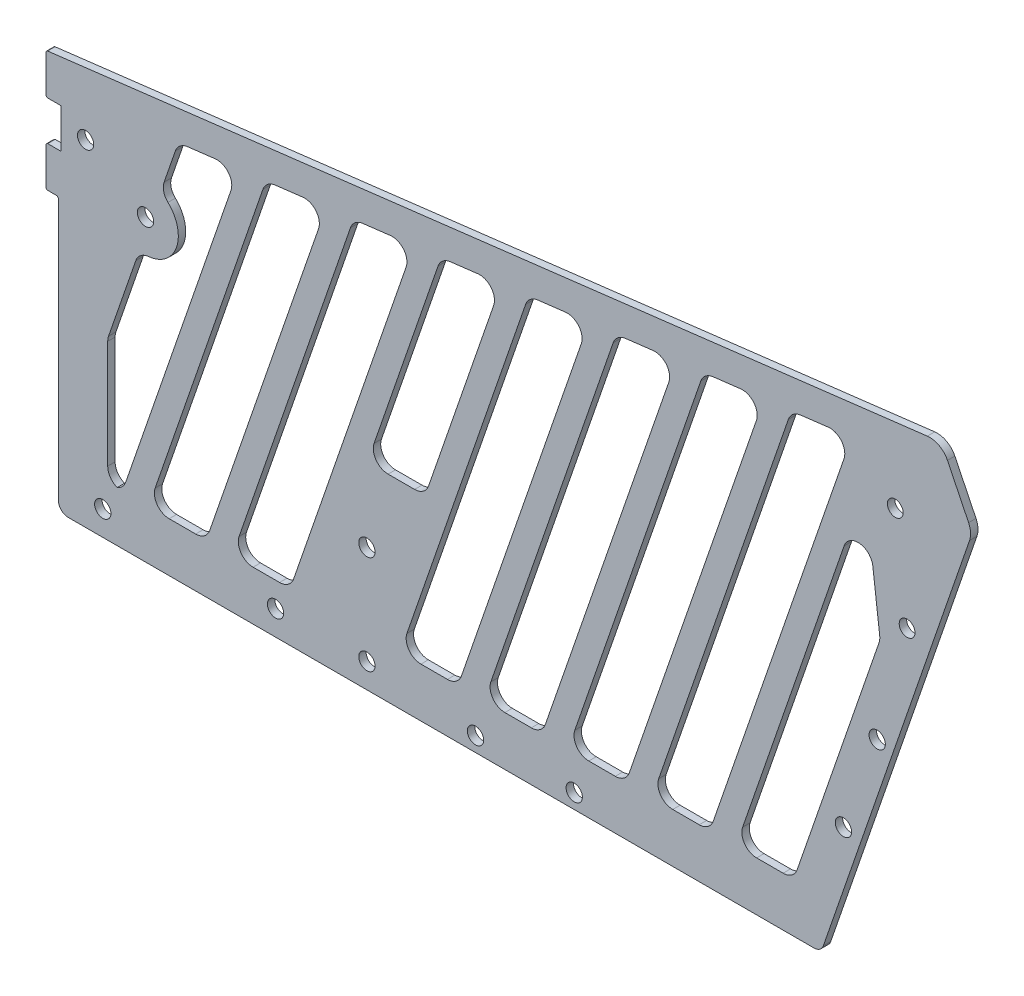
SolidWorks part; units mm, degrees
other "标注1"
sketch "草图8" plane through (190, 0, 1.5) normal (0.4662, -0.1687, 0.8685) x (0.883, 0.0286, -0.4684)
material "自定义塑料"
ref_plane "前视基准面" through (0, 0, 0) normal (0, 0, 1) x (1, 0, 0)
ref_plane "上视基准面" through (0, 0, 0) normal (0, 1, 0) x (1, 0, 0)
ref_plane "右视基准面" through (0, 0, 0) normal (1, 0, 0) x (0, 0, -1)
sketch "草图1" plane through (0, 0, 0) normal (0, 0, 1) x (1, 0, 0)
  line L0 (44, 5) -> (9, 5) construction
  line L1 (0, 0) -> (49, 0)
  line L2 (0, 0) -> (0, 80)
  line L5 (49, 0) -> (154.5, 0)
  line L6 (154.5, 0) -> (190, 102.9694)
  line L7 (0, 80) -> (190, 102.9694)
  circle A0 centre (44, 5) radius 1.65
  circle A1 centre (9, 5) radius 1.65
  circle A2 centre (62.5, 5) radius 1.65
  circle A3 centre (62.5, 25) radius 1.65
  circle A4 centre (84.5, 3) radius 1.65
  circle A5 centre (104.5, 3) radius 1.65
  circle A6 centre (159.0292, 24.1724) radius 1.65
  circle A7 centre (165.8696, 42.9663) radius 1.65
  circle A8 centre (5.5167, 68) radius 1.65
  point P9 (173.819, 56.0356)
  dimension "D3" = 3.3
  dimension "D4" = 190
  dimension "D1" = 49
  dimension "D2" = 80
  dimension "D5" = 5
  dimension "D6" = 35
  dimension "D7" = 105.5
extrude "凸台-拉伸1" add sketch "草图1" along normal blind 1.5
sketch "草图2" plane through (0, 0, 0) normal (0, 0, -1) x (-1, 0, 0)
  circle A0 centre (-17.6548, 60.5226) radius 1.65
  dimension "D1" = 3.3
  dimension "D2" = 60.5226
  dimension "D3" = 17.6548
extrude "切除-拉伸1" cut sketch "草图2" against normal through all
sketch "草图5" plane through (0, 0, 1.5) normal (0, 0, 1) x (1, 0, 0)
  line L0 (0, 80) -> (0, 0) construction
  line L1 (0, 0) -> (154.5, 0) construction
  circle A0 centre (169.5262, 85.385) radius 1.6
  circle A1 centre (171.9266, 65.5296) radius 1.6
  dimension "D1" = 3.2
  dimension "D2" = 169.5262
  dimension "D3" = 171.9266
  dimension "D4" = 65.5296
  dimension "D5" = 85.385
extrude "切除-拉伸3" cut sketch "草图5" against normal through all
sketch "草图6" plane through (0, 0, 0) normal (0, 0, -1) x (-1, 0, 0)
  line L0 (-154.5, 10) -> (0, 10)
  line L1 (-10, 0) -> (-10, 80)
  line L2 (-0.7201, 74.0434) -> (-181.2031, 95.8622)
  line L3 (-181.2031, 95.8622) -> (-148.8277, 1.9556)
  line L4 (0, 0) -> (0, 80)
  line L5 (-154.5, 0) -> (0, 0)
  line L6 (-190, 102.9694) -> (-154.5, 0)
  line L7 (0, 80) -> (-190, 102.9694)
  line L8 (0, 0) -> (0, 80)
  line L9 (-154.5, 0) -> (0, 0)
  line L10 (-190, 102.9694) -> (-154.5, 0)
  line L11 (0, 80) -> (-190, 102.9694)
  line L12 (-162.4894, 93.5999) -> (-167.1453, 55.0868)
  line L13 (-164.2031, 95.8622) -> (-131.8277, 1.9556)
  line L14 (-147.2031, 95.8622) -> (-114.8277, 1.9556)
  line L15 (-130.2031, 95.8622) -> (-97.8277, 1.9556)
  line L16 (-113.2031, 95.8622) -> (-80.8277, 1.9556)
  line L17 (-96.2031, 95.8622) -> (-63.8277, 1.9556)
  line L18 (-79.2031, 95.8622) -> (-46.8277, 1.9556)
  line L19 (-62.2031, 95.8622) -> (-29.8277, 1.9556)
  line L20 (-45.2031, 95.8622) -> (-12.8277, 1.9556)
  line L21 (-28.2031, 95.8622) -> (4.1723, 1.9556)
  line L22 (-166.5666, 95.0474) -> (-134.1912, 1.1408)
  line L23 (-149.5666, 95.0474) -> (-117.1912, 1.1408)
  line L24 (-132.5666, 95.0474) -> (-100.1912, 1.1408)
  line L25 (-115.5666, 95.0474) -> (-83.1912, 1.1408)
  line L26 (-98.5666, 95.0474) -> (-66.1912, 1.1408)
  line L27 (-81.5666, 95.0474) -> (-49.1912, 1.1408)
  line L28 (-64.5666, 95.0474) -> (-32.1912, 1.1408)
  line L29 (-47.5666, 95.0474) -> (-15.1912, 1.1408)
  line L30 (-30.5666, 95.0474) -> (1.8088, 1.1408)
  line L31 (-161.8397, 96.6771) -> (-129.4642, 2.7705)
  line L32 (-144.8397, 96.6771) -> (-112.4642, 2.7705)
  line L33 (-127.8397, 96.6771) -> (-95.4642, 2.7705)
  line L34 (-110.8397, 96.6771) -> (-78.4642, 2.7705)
  line L35 (-93.8397, 96.6771) -> (-61.4642, 2.7705)
  line L36 (-76.8397, 96.6771) -> (-44.4642, 2.7705)
  line L37 (-59.8397, 96.6771) -> (-27.4642, 2.7705)
  line L38 (-42.8397, 96.6771) -> (-10.4642, 2.7705)
  line L39 (-25.8397, 96.6771) -> (6.5358, 2.7705)
  line L40 (-178.8397, 96.6771) -> (-146.4642, 2.7705)
  circle A0 centre (-169.5262, 85.385) radius 1.6 construction
  circle A1 centre (-171.9266, 65.5296) radius 1.6 construction
  circle A2 centre (-165.8696, 42.9663) radius 1.5 construction
  circle A3 centre (-159.0292, 24.1724) radius 1.5 construction
  circle A4 centre (-104.5, 3) radius 1.65 construction
  circle A5 centre (-84.5, 3) radius 1.65 construction
  circle A6 centre (-62.5, 5) radius 1.65 construction
  circle A7 centre (-44, 5) radius 1.65 construction
  circle A8 centre (-62.5, 25) radius 1.65 construction
  circle A9 centre (-9, 5) radius 1.65 construction
  circle A10 centre (-17.6548, 60.5226) radius 1.65 construction
  circle A11 centre (-5.5167, 68) radius 1.65 construction
  circle A12 centre (-169.5262, 85.385) radius 1.6
  circle A13 centre (-171.9266, 65.5296) radius 1.6
  circle A14 centre (-165.8696, 42.9663) radius 1.5
  circle A15 centre (-159.0292, 24.1724) radius 1.5
  circle A16 centre (-104.5, 3) radius 1.65
  circle A17 centre (-84.5, 3) radius 1.65
  circle A18 centre (-62.5, 5) radius 1.65
  circle A19 centre (-44, 5) radius 1.65
  circle A20 centre (-62.5, 25) radius 1.65
  circle A21 centre (-9, 5) radius 1.65
  circle A22 centre (-17.6548, 60.5226) radius 1.65
  circle A23 centre (-5.5167, 68) radius 1.65
  circle A24 centre (-17.6548, 60.5226) radius 6.65
  circle A25 centre (-62.5, 25) radius 6.65
  dimension "D5" = 6
  dimension "D11" = 13.5717
  dimension "D1" = 0
  dimension "D2" = 10
  dimension "D3" = 10
  dimension "D4" = 6
  dimension "D7" = 2.5
  dimension "D8" = 2.5
  dimension "D9" = 5
  dimension "D10" = 2.5
  dimension "D6" = 10
extrude "切除-拉伸4" cut sketch "草图6" against normal blind 10 contours A24 L30 L2 L38 L0 L1 | L2 L37 L0 L29 | L2 L36 L0 L28 | A25 L27 L2 L35 | L2 L34 L0 L26 | L2 L33 L0 L25 | L2 L32 L0 L24 | L2 L31 L0 L23 | L22 L12 L3 L0 region at (153.7758, 42.0864, 0) region at (140.3654, 51.3238, 0) region at (122.9962, 50.2516, 0) region at (105.627, 49.1793, 0) region at (88.2579, 48.1071, 0) region at (74.454, 57.0811, 0) region at (20.6801, 46.912, 0) region at (53.5197, 45.9626, 0) region at (36.1506, 44.8904, 0)
fillet "圆角3" radius 3 37 edges at (89.747, 84.806, 0.75) (77.5264, 83.3286, 0.75) (69.2455, 10, 0.75) (80.9567, 10, 0.75) (107.4863, 86.9505, 0.75) (95.2658, 85.4731, 0.75) (18.2455, 10, 0.75) (29.9567, 10, 0.75) (54.2682, 80.5169, 0.75) (42.0477, 79.0395, 0.75) (35.2455, 10, 0.75) (46.9567, 10, 0.75) (72.0076, 82.6614, 0.75) (59.7871, 81.1841, 0.75) (120.2455, 10, 0.75) (131.9567, 10, 0.75) (160.7044, 93.3841, 0.75) (148.4839, 91.9067, 0.75) (16.4115, 53.9898, 0.75) (10, 35.3929, 0.75) (10, 10, 0.75) (12.9567, 10, 0.75) (36.5289, 78.3723, 0.75) (24.3084, 76.895, 0.75) (20.7016, 66.4335, 0.75) (103.2455, 10, 0.75) (114.9567, 10, 0.75) (142.965, 91.2396, 0.75) (130.7445, 89.7622, 0.75) (86.2455, 10, 0.75) (97.9567, 10, 0.75) (125.2257, 89.095, 0.75) (113.0051, 87.6177, 0.75) (163.4184, 85.9157, 0.75) (137.2455, 10, 0.75) (166.4588, 60.7657, 0.75) (148.9567, 10, 0.75)
fillet "圆角4" radius 5 1 edges at (69.1497, 25.0627, 0.75)
sketch "草图7" plane through (0, 0, 1.5) normal (0, 0, 1) x (1, 0, 0)
  line L1 (76.1407, 40) -> (59.1407, 40)
  line L2 (76.1407, 40) -> (76.1407, 30)
  line L3 (76.1407, 30) -> (59.1407, 30)
  line L4 (59.1407, 40) -> (59.1407, 30)
  line L6 (0, 0) -> (154.5, 0) construction
  line L7 (94.6538, 83.698) -> (70.6169, 13.9778) construction
  dimension "D1" = 40
  dimension "D2" = 17
  dimension "D3" = 10
extrude "凸台-拉伸2" add sketch "草图7" against normal up to surface (1.5 mm away) up to face at (88.1355, 48.0309, 0)
fillet "圆角5" radius 3 2 edges at (74.2996, 40, 0.75) (62.5884, 40, 0.75)
fillet "圆角7" radius 2 3 edges at (154.5, 0, 0.75) (0, 0, 0.75) (0, 80, 0.75)
chamfer "倒角1" distance 15 angle 45 1 edges at (190, 102.9694, 0.75) first distance on face at (172.4824, 52.1587, 0.75)
fillet "圆角8" radius 4 2 edges at (178.8576, 101.6224, 0.75) (185.111, 88.7885, 0.75)
sketch "草图9" plane through (0, 0, 1.5) normal (0, 0, 1) x (1, 0, 0)
  line L0 (0, 78.2272) -> (0, 2) construction
  line L1 (-0.5, 63.5) -> (0.5, 63.5)
  line L2 (-0.5, 63.5) -> (-0.5, 71.5)
  line L3 (-0.5, 71.5) -> (0.5, 71.5)
  line L4 (0.5, 63.5) -> (0.5, 71.5)
  line L5 (-0.5, 63.5) -> (0.5, 71.5) construction
  line L6 (-0.5, 71.5) -> (0.5, 63.5) construction
  circle A0 centre (5.5167, 68) radius 1.65 construction
  point P0 (0, 67.5)
  dimension "D2" = 4.5
  dimension "D1" = 3.5
  dimension "D3" = 0.5
extrude "切除-拉伸5" cut sketch "草图9" against normal blind 10
sketch "草图10" plane through (0, 0, 1.5) normal (0, 0, 1) x (1, 0, 0)
  line L0 (1.76, 80.2128) -> (-2.5, 79.6978)
  line L1 (-2.5, 79.6978) -> (-2.5, 71.5)
  line L2 (-2.5, 71.5) -> (0, 71.5)
  line L3 (0, 63.5) -> (-2.5, 63.5)
  line L4 (-2.5, 63.5) -> (-2.5, 55.3022)
  line L5 (-2.5, 55.3022) -> (0, 55.3022)
  line L6 (0, 63.5) -> (0, 2) construction
  line L7 (176.0295, 101.2805) -> (1.76, 80.2128) construction
  line L8 (0, 78.2272) -> (0, 71.5) construction
  line L9 (0, 78.2272) -> (0, 71.5)
  line L10 (0, 63.5) -> (0, 55.3022)
  arc A0 (1.76, 80.2128) -> (0, 78.2272) centre (2, 78.2272) ccw construction
  arc A1 (1.76, 80.2128) -> (0, 78.2272) centre (2, 78.2272) ccw
  dimension "D1" = 2.5
extrude "凸台-拉伸3" add sketch "草图10" against normal up to surface (1.5 mm away) up to face at (74.141, 57.8512, 0)
fillet "圆角9" radius 0.4 5 edges at (0, 55.3022, 0.75) (-2.5, 55.3022, 0.75) (-2.5, 63.5, 0.75) (-2.5, 71.5, 0.75) (-2.5, 79.6978, 0.75)
